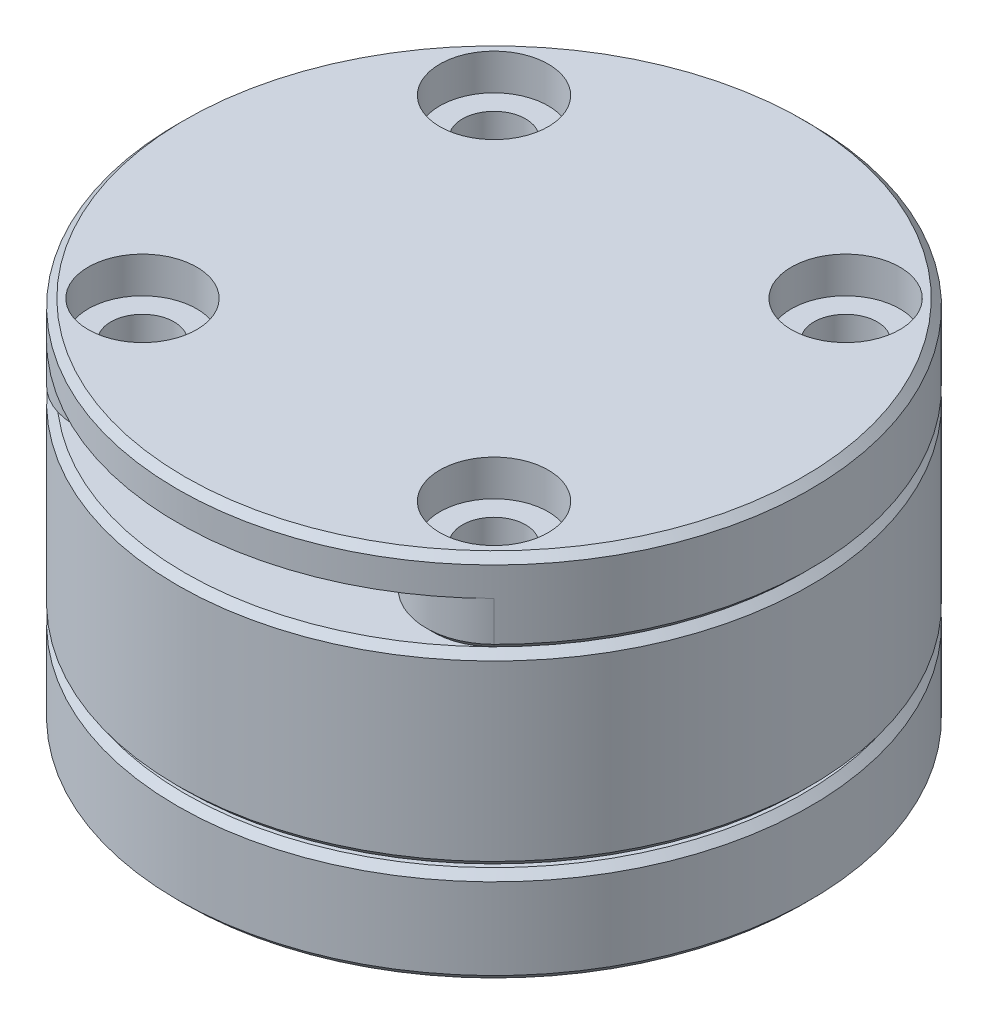
SolidWorks part; units mm, degrees
ref_plane "Front Plane" through (0, 0, 0) normal (0, 0, 1) x (1, 0, 0)
ref_plane "Top Plane" through (0, 0, 0) normal (0, 1, 0) x (1, 0, 0)
ref_plane "Right Plane" through (0, 0, 0) normal (1, 0, 0) x (0, 0, -1)
sketch "Sketch1" plane through (0, 0, 0) normal (0, 1, 0) x (1, 0, 0)
  circle A0 centre (0, 0) radius 17.5
  circle A1 centre (0, 0) radius 7.5 construction
  circle A2 centre (7.5, 0) radius 1.75
  circle A3 centre (0, 7.5) radius 1.75
  circle A4 centre (-7.5, 0) radius 1.75
  circle A5 centre (0, -7.5) radius 1.75
  dimension "D1" = 3.5
  dimension "D2" = 15
  dimension "D3" = 35
extrude "Main Boss" add sketch "Sketch1" along normal blind 5.287
sketch "Sketch3" plane through (0, 5.287, 0) normal (0, 1, 0) x (1, 0, 0)
  circle A0 centre (0, 0) radius 14.8987
  circle A2 centre (-7.5, 0) radius 1.75 construction
  circle A3 centre (0, -7.5) radius 1.75 construction
  circle A4 centre (7.5, 0) radius 1.75 construction
  circle A5 centre (0, 7.5) radius 1.75 construction
  circle A6 centre (-7.5, 0) radius 1.75
  circle A7 centre (0, -7.5) radius 1.75
  circle A8 centre (7.5, 0) radius 1.75
  circle A9 centre (0, 7.5) radius 1.75
  dimension "D1" = 29.7974
extrude "Codewheel Center Boss" add sketch "Sketch3" along normal blind 0.5
sketch "Sketch4" plane through (0, 5.287, 0) normal (0, 1, 0) x (1, 0, 0)
  circle A0 centre (0, 0) radius 16.5
  circle A1 centre (0, 0) radius 17.5 construction
  circle A2 centre (0, 0) radius 14.8987 construction
  circle A3 centre (0, 0) radius 14.8987
  dimension "D1" = 1
extrude "Codewheel Relief Cut" cut sketch "Sketch4" against normal blind 0.4
chamfer "Codewheel Relief Chamfer" distance 0.4 angle 45 1 edges at (0, 4.887, 16.5)
ref_plane "Plane1" through (0, 5.4648, 0) normal (0, 1, 0) x (1, 0, 0)
sketch "Sketch6" plane through (0, 5.4648, 0) normal (0, 1, 0) x (1, 0, 0)
  circle A0 centre (0, 0) radius 16.5 construction
  circle A1 centre (0, 0) radius 17.5 construction
  circle A2 centre (0, 0) radius 16.5
  circle A3 centre (0, 0) radius 17.5
extrude "Codewheel Top Boss" add sketch "Sketch6" along normal blind 0.4 separate body
sketch "Sketch7" plane through (0, 5.8648, 0) normal (0, 1, 0) x (1, 0, 0)
  circle A0 centre (0, 0) radius 17.5 construction
  circle A1 centre (0, 0) radius 17.5
  circle A2 centre (0, -7.5) radius 1.75 construction
  circle A3 centre (7.5, 0) radius 1.75 construction
  circle A4 centre (-7.5, 0) radius 1.75 construction
  circle A5 centre (0, 7.5) radius 1.75 construction
  circle A6 centre (0, -7.5) radius 1.75
  circle A7 centre (7.5, 0) radius 1.75
  circle A8 centre (-7.5, 0) radius 1.75
  circle A9 centre (0, 7.5) radius 1.75
extrude "Secondary Boss" add sketch "Sketch7" along normal blind 10
chamfer "Codewheel Relief Chamfer 2" distance 0.4 angle 45 1 edges at (0, 5.8648, 16.5)
sketch "Sketch8" plane through (0, 15.8648, 0) normal (0, 1, 0) x (1, 0, 0)
  circle A0 centre (-7.5, 0) radius 3
  circle A1 centre (0, 7.5) radius 3
  circle A2 centre (7.5, 0) radius 3
  circle A3 centre (0, -7.5) radius 3
  dimension "D1" = 6
extrude "Motor Bolt Countersinks" cut sketch "Sketch8" against normal blind 8
chamfer "Edge Chamfers 1" distance 0.4 angle 45 2 edges at (0, 0, 17.5) (0, 5.287, 17.5)
chamfer "Edge Chamfers 2" distance 0.4 angle 45 2 edges at (0, 15.8648, 17.5) (0, 5.4648, 17.5)
sketch "Sketch11" plane through (0, 15.8648, 0) normal (0, 1, 0) x (1, 0, 0)
  line L0 (0, 0) -> (0, -6.5) construction
  line L1 (-10.5, 5.5) -> (10.5, 5.5) construction
  line L2 (-10.5, 5.5) -> (-10.5, -6.5) construction
  line L3 (-10.5, -6.5) -> (10.5, -6.5) construction
  line L4 (10.5, 5.5) -> (10.5, -6.5) construction
  line L5 (-10.6, 5.6) -> (-10.6, -6.6)
  line L6 (-10.6, -6.6) -> (10.6, -6.6)
  line L7 (10.6, 5.6) -> (10.6, -6.6)
  line L8 (-10.6, 5.6) -> (10.6, 5.6)
  dimension "D1" = 21
  dimension "D2" = 6.5
  dimension "D3" = 5.5
  dimension "D4" = 0.1
extrude "Accelerometer Notch" cut sketch "Sketch11" against normal blind 1
sketch "Sketch12" plane through (0, 14.8648, 0) normal (0, 1, 0) x (1, 0, 0)
  line L0 (10.6, -6.6) -> (10.6, 5.6) construction
  line L1 (-10.6, -6.6) -> (10.6, -6.6)
  line L2 (-10.6, -6.6) -> (-10.6, -4.6)
  line L3 (-10.6, -4.6) -> (10.6, -4.6)
  line L4 (10.6, -6.6) -> (10.6, -4.6)
  dimension "D1" = 2
extrude "Accelerometer Pin Notch" cut sketch "Sketch12" against normal blind 1.6
fillet "Fillet1" radius 1 4 edges at (-2.8618, 14.5648, 6.6) (2.8618, 14.5648, 6.6) (-2.3216, 15.3648, -5.6) (2.3216, 15.3648, -5.6)
chamfer "Accelerometer Pin Notch Chamfer" distance 1.6 angle 45 2 edges at (-5.6841, 14.8648, 4.6) (5.6841, 14.8648, 4.6)
sketch "Sketch13" plane through (0, 15.8648, 0) normal (0, 1, 0) x (1, 0, 0)
  line L0 (-9.7227, 9.7227) -> (9.7227, -9.7227) construction
  line L1 (9.7227, -9.7227) -> (9.7227, 9.7227) construction
  line L2 (9.7227, 9.7227) -> (-9.7227, -9.7227) construction
  line L3 (-9.7227, -9.7227) -> (9.7227, -9.7227) construction
  circle A0 centre (0, 0) radius 13.75 construction
  circle A1 centre (9.7227, 9.7227) radius 2.35
  circle A2 centre (-9.7227, 9.7227) radius 2.35
  circle A3 centre (-9.7227, -9.7227) radius 2.35
  circle A4 centre (9.7227, -9.7227) radius 2.35
  dimension "D1" = 27.5
  dimension "D2" = 4.7
extrude "Accelerometer Layer Heat Set Insert Holes" cut sketch "Sketch13" against normal blind 4.2
sketch "Sketch14" plane through (0, 11.6648, 0) normal (0, 1, 0) x (1, 0, 0)
  circle A0 centre (-9.7227, 9.7227) radius 1.75
  circle A1 centre (9.7227, -9.7227) radius 1.75
  circle A2 centre (-9.7227, -9.7227) radius 1.75
  circle A3 centre (9.7227, 9.7227) radius 1.75
  circle A4 centre (9.7227, 9.7227) radius 2.35 construction
  dimension "D1" = 3.5
extrude "Accelerometer Layer Bolt Through Holes" cut sketch "Sketch14" against normal blind 5
sketch "Sketch15" plane through (0, 15.8648, 0) normal (0, 1, 0) x (1, 0, 0)
  line L0 (7.6464, -6.6) -> (10.6, -6.6)
  line L1 (-10.6, 5.6) -> (10.6, 5.6)
  line L2 (-10.6, 5.6) -> (-10.6, -6.6)
  line L3 (-10.6, -6.6) -> (-7.6464, -6.6)
  line L4 (10.6, 5.6) -> (10.6, -6.6)
  arc A0 (12.3744, -12.3744) -> (-12.3744, -12.3744) centre (0, 0) ccw
  circle A1 centre (0, 0) radius 17.5 construction
  circle A2 centre (-9.7227, -9.7227) radius 1.75 construction
  circle A3 centre (9.7227, -9.7227) radius 1.75 construction
  circle A4 centre (9.7227, 9.7227) radius 1.75 construction
  circle A5 centre (-9.7227, 9.7227) radius 1.75 construction
  circle A6 centre (-9.7227, -9.7227) radius 1.75
  circle A7 centre (9.7227, -9.7227) radius 1.75
  circle A8 centre (9.7227, 9.7227) radius 1.75
  circle A9 centre (-9.7227, 9.7227) radius 1.75
  arc A10 (-12.3744, -12.3744) -> (-7.6464, -6.6) centre (-9.7227, -9.7227) ccw
  arc A11 (7.6464, -6.6) -> (12.3744, -12.3744) centre (9.7227, -9.7227) ccw
extrude "Accelerometer Cover" add sketch "Sketch15" along normal blind 2.6 separate body
sketch "Sketch17" plane through (0, 18.4648, 0) normal (0, 1, 0) x (1, 0, 0)
  circle A0 centre (0, 0) radius 17.5
  arc A1 (12.3744, -12.3744) -> (-12.3744, -12.3744) centre (0, 0) ccw construction
  circle A2 centre (-9.7227, -9.7227) radius 1.75 construction
  circle A3 centre (-9.7227, 9.7227) radius 1.75 construction
  circle A4 centre (9.7227, 9.7227) radius 1.75 construction
  circle A5 centre (9.7227, -9.7227) radius 1.75 construction
  circle A6 centre (-9.7227, -9.7227) radius 1.75
  circle A7 centre (-9.7227, 9.7227) radius 1.75
  circle A8 centre (9.7227, 9.7227) radius 1.75
  circle A9 centre (9.7227, -9.7227) radius 1.75
extrude "Accelerometer Cover Boss" add sketch "Sketch17" along normal blind 2
sketch "Sketch19" plane through (0, 20.4648, 0) normal (0, 1, 0) x (1, 0, 0)
  circle A0 centre (-9.7227, 9.7227) radius 3
  circle A1 centre (9.7227, 9.7227) radius 3
  circle A2 centre (9.7227, -9.7227) radius 3
  circle A3 centre (-9.7227, -9.7227) radius 3
  dimension "D1" = 6
extrude "Acclerometer Cover Countersinks" cut sketch "Sketch19" against normal blind 2
chamfer "Edge Chamfers 3" distance 0.4 angle 45 4 edges at (0, 20.4648, 17.5) (6.8212, 15.8648, 12.0984) (-6.8212, 15.8648, 12.0984) (0, 15.8648, -17.5)
sketch "Sketch18" plane through (0, 20.4648, 0) normal (0, 1, 0) x (1, 0, 0)
  line L1 (4.3301, 7.5) -> (-4.3301, 7.5)
  line L2 (-4.3301, 7.5) -> (-8.6603, 0)
  line L3 (-8.6603, 0) -> (-4.3301, -7.5)
  line L4 (-4.3301, -7.5) -> (4.3301, -7.5)
  line L5 (4.3301, -7.5) -> (8.6603, 0)
  line L6 (8.6603, 0) -> (4.3301, 7.5)
  circle A0 centre (0, 0) radius 7.5 construction
  dimension "D1" = 15
extrude "Output Cone" [suppressed] add sketch "Sketch18" along normal blind 12.5 draft 5
chamfer "Chamfer1" [suppressed] distance 0.4 angle 45
